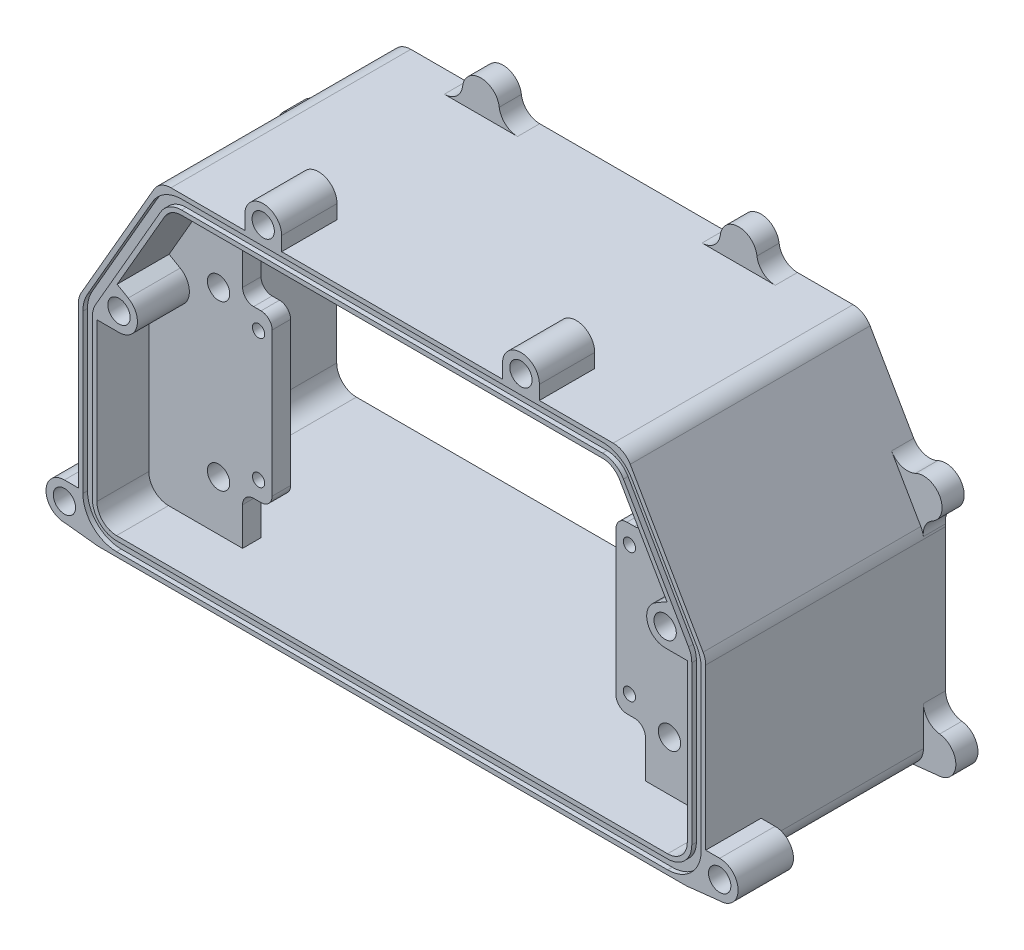
SolidWorks part; units mm, degrees
material "ABS"
ref_plane "X-Y Datum" through (0, 0, 0) normal (0, 0, 1) x (1, 0, 0)
ref_plane "X-Z Datum" through (0, 0, 0) normal (0, 1, 0) x (1, 0, 0)
ref_plane "Y-Z Datum" through (0, 0, 0) normal (1, 0, 0) x (0, 0, -1)
sketch "Sketch1" plane through (0, 0, 0) normal (0, 0, 1) x (1, 0, 0)
  line L0 (-85, -47) -> (-77.6291, 47)
  line L1 (-85, 47) -> (85, 47)
  line L2 (-85, 47) -> (-85, -47)
  line L3 (-85, -47) -> (85, -47)
  line L4 (85, 47) -> (85, -47)
  line L5 (-85, 47) -> (85, -47) construction
  line L6 (-85, -47) -> (85, 47) construction
  line L8 (0, 90.3576) -> (0, -90.3576) construction
  line L9 (85, -47) -> (77.6291, 47)
  point P0 (0, 0)
  point P12 (0, 0)
  dimension "D1" = 170
  dimension "D2" = 94
extrude "Boss-Extrude1" add sketch "Sketch1" along normal mid plane 65 contours L3 L9 L1 L0 | L1 L2 L0 | L9 L4 L1
sketch "Sketch2" plane through (0, 0, -32.5) normal (0, 0, -1) x (-1, 0, 0)
  line L0 (-85, 8.88) -> (-63, 47)
  line L1 (-85, 47) -> (-85, -47) construction
  line L2 (85, 47) -> (-85, 47) construction
  line L3 (0, -14.0019) -> (0, 14.0019) construction
  line L4 (85, 8.88) -> (63, 47)
  point P11 (0, 0)
  line M3 (-85, 47) -> (-85, -47)
  line M5 (85, -47) -> (85, 47)
  line M6 (85, 47) -> (-85, 47)
  dimension "D1" = 55.88
  dimension "D2" = 22
extrude "Cut-Extrude1" cut sketch "Sketch2" against normal through all contours L0 M3 M6 | L4 M5 M6
shell "Shell1" thickness 5
sketch "Sketch4" plane through (0, 0, 27.5) normal (0, 0, -1) x (-1, 0, 0)
  line L6 (-60.1127, 42) -> (-80, 7.5407)
  line L7 (-80, 7.5407) -> (-80, -42)
  line L8 (-80, -42) -> (80, -42)
  line L9 (80, -42) -> (80, 7.5407)
  line L10 (-60.1127, 42) -> (-80, 7.5407)
  line L11 (60.1127, 42) -> (-60.1127, 42)
  line L13 (-80, 7.5407) -> (-80, -42)
  line L14 (-80, -42) -> (80, -42)
  line L15 (80, -42) -> (80, 7.5407)
  line L17 (60.1127, 42) -> (-60.1127, 42)
  line L18 (80, 7.5407) -> (60.1127, 42)
  line L19 (80, 7.5407) -> (60.1127, 42)
  dimension "D1" = 0
extrude "Cut-Extrude2" cut sketch "Sketch4" against normal through all
fillet "Fillet1" radius 5.334 12 edges at (85, 8.88, 0) (63, 47, 0) (-85, 8.88, 0) (-63, 47, 0) (60.1127, 42, 0) (-80, 7.5407, 0) (-80, -42, 0) (80, -42, 0) (-60.1127, 42, 0) (80, 7.5407, 0) (-85, -47, 0) (85, -47, 0)
sketch "Sketch5" plane through (0, 0, 32.5) normal (0, 0, 1) x (1, 0, 0)
  line L44 (-83.7827, 6.1119) -> (-83.7827, -36.666)
  line L45 (-74.666, -45.7827) -> (74.666, -45.7827)
  line L46 (83.7827, -36.666) -> (83.7827, 6.1119)
  line L47 (82.5621, 10.669) -> (64.9286, 41.223)
  line L48 (57.0325, 45.7827) -> (-57.0325, 45.7827)
  line L49 (-64.9286, 41.223) -> (-82.5621, 10.669)
  line L50 (-82.5, 6.1119) -> (-82.5, -36.666)
  line L51 (-74.666, -44.5) -> (74.666, -44.5)
  line L52 (82.5, -36.666) -> (82.5, 6.1119)
  line L53 (81.4511, 10.0278) -> (63.8176, 40.5819)
  line L54 (57.0325, 44.5) -> (-57.0325, 44.5)
  line L55 (-63.8176, 40.5819) -> (-81.4511, 10.0278)
  line L56 (-82.5, 6.1119) -> (-82.5, -36.666) construction
  line L57 (-74.666, -44.5) -> (74.666, -44.5) construction
  line L58 (82.5, -36.666) -> (82.5, 6.1119) construction
  line L59 (81.4511, 10.0278) -> (63.8176, 40.5819) construction
  line L60 (57.0325, 44.5) -> (-57.0325, 44.5) construction
  line L61 (-63.8176, 40.5819) -> (-81.4511, 10.0278) construction
  line L62 (-62.7066, 39.9407) -> (-80.3401, 9.3866)
  line L63 (-81.2173, 6.1119) -> (-81.2173, -36.666)
  line L64 (-74.666, -43.2173) -> (74.666, -43.2173)
  line L65 (81.2173, -36.666) -> (81.2173, 6.1119)
  line L66 (80.3401, 9.3866) -> (62.7066, 39.9407)
  line L67 (57.0325, 43.2173) -> (-57.0325, 43.2173)
  arc A34 (-83.7827, -36.666) -> (-74.666, -45.7827) centre (-74.666, -36.666) ccw
  arc A35 (74.666, -45.7827) -> (83.7827, -36.666) centre (74.666, -36.666) ccw
  arc A36 (83.7827, 6.1119) -> (82.5621, 10.669) centre (74.666, 6.1119) ccw
  arc A37 (64.9286, 41.223) -> (57.0325, 45.7827) centre (57.0325, 36.666) ccw
  arc A38 (-57.0325, 45.7827) -> (-64.9286, 41.223) centre (-57.0325, 36.666) ccw
  arc A39 (-82.5621, 10.669) -> (-83.7827, 6.1119) centre (-74.666, 6.1119) ccw
  arc A40 (-81.4511, 10.0278) -> (-82.5, 6.1119) centre (-74.666, 6.1119) ccw
  arc A41 (-82.5, -36.666) -> (-74.666, -44.5) centre (-74.666, -36.666) ccw
  arc A42 (82.5, 6.1119) -> (81.4511, 10.0278) centre (74.666, 6.1119) ccw
  arc A43 (74.666, -44.5) -> (82.5, -36.666) centre (74.666, -36.666) ccw
  arc A44 (63.8176, 40.5819) -> (57.0325, 44.5) centre (57.0325, 36.666) ccw
  arc A45 (-57.0325, 44.5) -> (-63.8176, 40.5819) centre (-57.0325, 36.666) ccw
  arc A46 (-81.4511, 10.0278) -> (-82.5, 6.1119) centre (-74.666, 6.1119) ccw construction
  arc A47 (-82.5, -36.666) -> (-74.666, -44.5) centre (-74.666, -36.666) ccw construction
  arc A48 (82.5, 6.1119) -> (81.4511, 10.0278) centre (74.666, 6.1119) ccw construction
  arc A49 (74.666, -44.5) -> (82.5, -36.666) centre (74.666, -36.666) ccw construction
  arc A50 (63.8176, 40.5819) -> (57.0325, 44.5) centre (57.0325, 36.666) ccw construction
  arc A51 (-57.0325, 44.5) -> (-63.8176, 40.5819) centre (-57.0325, 36.666) ccw construction
  arc A52 (-80.3401, 9.3866) -> (-81.2173, 6.1119) centre (-74.666, 6.1119) ccw
  arc A53 (-81.2173, -36.666) -> (-74.666, -43.2173) centre (-74.666, -36.666) ccw
  arc A54 (74.666, -43.2173) -> (81.2173, -36.666) centre (74.666, -36.666) ccw
  arc A55 (81.2173, 6.1119) -> (80.3401, 9.3866) centre (74.666, 6.1119) ccw
  arc A56 (62.7066, 39.9407) -> (57.0325, 43.2173) centre (57.0325, 36.666) ccw
  arc A57 (-57.0325, 43.2173) -> (-62.7066, 39.9407) centre (-57.0325, 36.666) ccw
  dimension "D1" = 2.5
  dimension "D2" = 1.2827
  dimension "D3" = 1.2827
extrude "Cut-Extrude3" cut sketch "Sketch5" against normal blind 1.2446
mirror "Mirror1" about plane through (0, 0, 0) normal (0, 0, 1) of "Cut-Extrude3"
sketch "Sketch7" plane through (0, 0, 32.5) normal (0, 0, 1) x (1, 0, 0)
  line L0 (0, 28.7255) -> (0, -28.7255) construction
  line L1 (83.7827, -36.666) -> (83.7827, 6.1119) construction
  line L2 (-79.666, -47) -> (79.666, -47) construction
  line L3 (88.7827, -36) -> (85, -36)
  line L4 (-57.0325, 42) -> (57.0325, 42) construction
  line L5 (85, 7.4512) -> (85, -41.666) construction
  line L6 (-88.7827, -36) -> (-85, -36)
  line L7 (88.7827, -46) -> (79.666, -47)
  line L8 (-88.7827, -46) -> (-79.666, -47)
  line L9 (80, 6.1119) -> (80, -36.666) construction
  line L10 (-59.9198, 47) -> (59.9198, 47) construction
  line L11 (74.504, 17.0638) -> (71.5007, 15.3305)
  line L12 (61.6523, 39.3322) -> (79.2858, 8.7782) construction
  line L13 (-74.504, 17.0638) -> (-71.5007, 15.3305)
  line L14 (-79.2858, 8.7782) -> (-61.6523, 39.3322) construction
  line L15 (74, 6) -> (80, 6)
  line L16 (57.0325, 45.7827) -> (-57.0325, 45.7827) construction
  line L17 (39.9198, 50.7827) -> (39.9198, 47)
  line L18 (-74, 6) -> (-80, 6)
  line L19 (-39.9198, 50.7827) -> (-39.9198, 47)
  line L20 (29.9198, 50.7827) -> (29.9198, 47)
  line L21 (-29.9198, 50.7827) -> (-29.9198, 47)
  line L22 (-80, -36.666) -> (-80, 6.1119) construction
  line L23 (74.666, -42) -> (-74.666, -42) construction
  line L24 (-57.0325, 42) -> (57.0325, 42)
  line L25 (-79.2858, 8.7782) -> (-61.6523, 39.3322)
  line L26 (-80, -36.666) -> (-80, 6.1119)
  line L27 (74.666, -42) -> (-74.666, -42)
  line L28 (80, 6.1119) -> (80, -36.666)
  line L29 (61.6523, 39.3322) -> (79.2858, 8.7782)
  line L30 (85, 7.4512) -> (85, -41.666)
  line L31 (-59.9198, 47) -> (59.9198, 47)
  line L32 (-85, 7.4512) -> (-85, -41.666) construction
  line L33 (-85, 7.4512) -> (-85, -41.666)
  circle A0 centre (88.7827, -41) radius 3.025
  circle A1 centre (34.9198, 50.7827) radius 3.025
  circle A2 centre (74, 11) radius 3.025
  circle A3 centre (88.7827, -41) radius 5
  circle A4 centre (74, 11) radius 5
  circle A5 centre (34.9198, 50.7827) radius 5
  circle A6 centre (-88.7827, -41) radius 3.025
  circle A7 centre (-88.7827, -41) radius 5
  circle A8 centre (-74, 11) radius 3.025
  circle A9 centre (-74, 11) radius 5
  circle A10 centre (-34.9198, 50.7827) radius 5
  circle A11 centre (-34.9198, 50.7827) radius 3.025
  arc A12 (61.6523, 39.3322) -> (57.0325, 42) centre (57.0325, 36.666) ccw construction
  arc A13 (-57.0325, 42) -> (-61.6523, 39.3322) centre (-57.0325, 36.666) ccw construction
  arc A14 (-79.2858, 8.7782) -> (-80, 6.1119) centre (-74.666, 6.1119) ccw construction
  arc A15 (-80, -36.666) -> (-74.666, -42) centre (-74.666, -36.666) ccw construction
  arc A16 (74.666, -42) -> (80, -36.666) centre (74.666, -36.666) ccw construction
  arc A17 (80, 6.1119) -> (79.2858, 8.7782) centre (74.666, 6.1119) ccw construction
  arc A18 (61.6523, 39.3322) -> (57.0325, 42) centre (57.0325, 36.666) ccw
  arc A19 (-57.0325, 42) -> (-61.6523, 39.3322) centre (-57.0325, 36.666) ccw
  arc A20 (-79.2858, 8.7782) -> (-80, 6.1119) centre (-74.666, 6.1119) ccw
  arc A21 (-80, -36.666) -> (-74.666, -42) centre (-74.666, -36.666) ccw
  arc A22 (74.666, -42) -> (80, -36.666) centre (74.666, -36.666) ccw
  arc A23 (80, 6.1119) -> (79.2858, 8.7782) centre (74.666, 6.1119) ccw
  arc A24 (79.666, -47) -> (85, -41.666) centre (79.666, -41.666) ccw construction
  arc A25 (79.666, -47) -> (85, -41.666) centre (79.666, -41.666) ccw
  arc A26 (-85, -41.666) -> (-79.666, -47) centre (-79.666, -41.666) ccw construction
  arc A27 (-85, -41.666) -> (-79.666, -47) centre (-79.666, -41.666) ccw
  point P17 (0, 0)
  point P53 (74, 11)
  point P57 (59.9198, 47)
  point P58 (-59.9198, 47)
  arc M14 (79.666, -47) -> (85, -41.666) centre (79.666, -41.666) ccw
  line M15 (85, -41.666) -> (85, 7.4512)
  line M19 (59.9198, 47) -> (-59.9198, 47)
  dimension "D1" = 6.05
  dimension "D2" = 10
  dimension "D3" = 5
  dimension "D4" = 6
  dimension "D5" = 6
  dimension "D6" = 36
  dimension "D7" = 5
  dimension "D8" = 25
extrude "Boss-Extrude2" add sketch "Sketch7" against normal blind 15 contours A3 L7 M14 | A3 A0 M15 M14 | A3 L3 L30 | A3 M15 M14 | L28 A23 L29 A4 L15 | L29 A4 A2 | A4 L29 L11 | A2 | A0 | A1 | A5 L31 A1 | A5 L17 M19 | A5 L20 M19
sketch "Sketch8" plane through (0, 0, 32.5) normal (0, 0, 1) x (1, 0, 0)
  line L0 (88.7827, -46) -> (79.666, -47) construction
  line L1 (85, 7.4512) -> (85, -41.666) construction
  line L2 (-88.7827, -36) -> (-85, -36) construction
  line L3 (88.7827, -36) -> (85, -36) construction
  line L4 (-88.7827, -46) -> (-79.666, -47) construction
  line L5 (-85, 7.4512) -> (-85, -41.666) construction
  line L6 (-74.666, -42) -> (74.666, -42)
  line L7 (-80, 6.1119) -> (-80, -36.666)
  line L8 (-61.6523, 39.3322) -> (-79.2858, 8.7782)
  line L9 (57.0325, 42) -> (-57.0325, 42)
  line L10 (79.2858, 8.7782) -> (61.6523, 39.3322)
  line L11 (80, -36.666) -> (80, 6.1119)
  line L12 (-74.666, -42) -> (74.666, -42)
  line L13 (-80, 6.1119) -> (-80, -36.666)
  line L14 (-61.6523, 39.3322) -> (-79.2858, 8.7782)
  line L15 (57.0325, 42) -> (-57.0325, 42)
  line L16 (79.2858, 8.7782) -> (61.6523, 39.3322)
  line L17 (80, -36.666) -> (80, 6.1119)
  line L18 (-59.9198, 47) -> (59.9198, 47) construction
  line L19 (-74.504, 17.0638) -> (-71.5007, 15.3305) construction
  line L20 (74.504, 17.0638) -> (71.5007, 15.3305) construction
  line L21 (29.9198, 50.7827) -> (29.9198, 47) construction
  line L22 (-39.9198, 50.7827) -> (-39.9198, 47) construction
  line L23 (-74, 6) -> (-80, 6) construction
  line L24 (39.9198, 50.7827) -> (39.9198, 47) construction
  line L25 (74, 6) -> (80, 6) construction
  line L26 (-29.9198, 50.7827) -> (-29.9198, 47) construction
  line L27 (88.7827, -46) -> (79.666, -47)
  line L28 (85, 7.4512) -> (85, -41.666)
  line L29 (-88.7827, -36) -> (-85, -36)
  line L30 (88.7827, -36) -> (85, -36)
  line L31 (-88.7827, -46) -> (-79.666, -47)
  line L32 (-85, 7.4512) -> (-85, -41.666)
  line L33 (-59.9198, 47) -> (59.9198, 47)
  line L34 (-74.504, 17.0638) -> (-71.5007, 15.3305)
  line L35 (74.504, 17.0638) -> (71.5007, 15.3305)
  line L36 (29.9198, 50.7827) -> (29.9198, 47)
  line L37 (-39.9198, 50.7827) -> (-39.9198, 47)
  line L38 (-74, 6) -> (-80, 6)
  line L39 (39.9198, 50.7827) -> (39.9198, 47)
  line L40 (74, 6) -> (80, 6)
  line L41 (-29.9198, 50.7827) -> (-29.9198, 47)
  arc A0 (79.666, -47) -> (85, -41.666) centre (79.666, -41.666) ccw construction
  circle A1 centre (-74, 11) radius 3.025
  circle A2 centre (-74, 11) radius 3.025
  circle A3 centre (-88.7827, -41) radius 5
  circle A4 centre (-88.7827, -41) radius 5
  circle A5 centre (-88.7827, -41) radius 3.025
  circle A6 centre (-88.7827, -41) radius 3.025
  circle A7 centre (34.9198, 50.7827) radius 5
  circle A8 centre (34.9198, 50.7827) radius 5
  circle A9 centre (74, 11) radius 5
  circle A10 centre (74, 11) radius 5
  circle A11 centre (88.7827, -41) radius 5
  circle A12 centre (88.7827, -41) radius 5
  circle A13 centre (74, 11) radius 3.025
  circle A14 centre (74, 11) radius 3.025
  circle A15 centre (34.9198, 50.7827) radius 3.025
  circle A16 centre (34.9198, 50.7827) radius 3.025
  circle A17 centre (88.7827, -41) radius 3.025
  circle A18 centre (88.7827, -41) radius 3.025
  circle A19 centre (-34.9198, 50.7827) radius 3.025
  circle A20 centre (-34.9198, 50.7827) radius 3.025
  circle A21 centre (-34.9198, 50.7827) radius 5
  circle A22 centre (-34.9198, 50.7827) radius 5
  circle A23 centre (-74, 11) radius 5
  circle A24 centre (-74, 11) radius 5
  arc A25 (-85, -41.666) -> (-79.666, -47) centre (-79.666, -41.666) ccw construction
  arc A26 (79.666, -47) -> (85, -41.666) centre (79.666, -41.666) ccw
  arc A27 (-85, -41.666) -> (-79.666, -47) centre (-79.666, -41.666) ccw
  arc A30 (-80, -36.666) -> (-74.666, -42) centre (-74.666, -36.666) ccw
  arc A31 (-79.2858, 8.7782) -> (-80, 6.1119) centre (-74.666, 6.1119) ccw
  arc A32 (-57.0325, 42) -> (-61.6523, 39.3322) centre (-57.0325, 36.666) ccw
  arc A33 (61.6523, 39.3322) -> (57.0325, 42) centre (57.0325, 36.666) ccw
  arc A34 (80, 6.1119) -> (79.2858, 8.7782) centre (74.666, 6.1119) ccw
  arc A35 (74.666, -42) -> (80, -36.666) centre (74.666, -36.666) ccw
  arc A36 (-80, -36.666) -> (-74.666, -42) centre (-74.666, -36.666) ccw
  arc A37 (-79.2858, 8.7782) -> (-80, 6.1119) centre (-74.666, 6.1119) ccw
  arc A38 (-57.0325, 42) -> (-61.6523, 39.3322) centre (-57.0325, 36.666) ccw
  arc A39 (61.6523, 39.3322) -> (57.0325, 42) centre (57.0325, 36.666) ccw
  arc A40 (80, 6.1119) -> (79.2858, 8.7782) centre (74.666, 6.1119) ccw
  arc A41 (74.666, -42) -> (80, -36.666) centre (74.666, -36.666) ccw
  dimension "D1" = 0
  dimension "D2" = 0
  dimension "D3" = 0
  dimension "D4" = 0
  dimension "D5" = 0
  dimension "D6" = 0
  dimension "D7" = 0
  dimension "D8" = 0
  dimension "D9" = 0
  dimension "D10" = 0
  dimension "D11" = 0
  dimension "D12" = 0
  dimension "D13" = 0
extrude "Cut-Extrude4" cut sketch "Sketch8" against normal blind 8 contours A16 | A14 | A18
mirror "Mirror2" about plane through (0, 0, 0) normal (1, 0, 0) of "Cut-Extrude4", "Boss-Extrude2"
ref_plane "Plane1" through (0, 0, 18.42) normal (0, 0, -1) x (-1, 0, 0)
sketch "Sketch9" plane through (0, 0, 18.42) normal (0, 0, -1) x (-1, 0, 0)
  line L0 (61.09, 15.9688) -> (61.09, -28.4812) construction
  line L1 (74.666, -42) -> (-74.666, -42) construction
  line L2 (54.59, -42) -> (67.59, -42)
  line L3 (54.59, -42) -> (54.59, 29.0439)
  line L4 (54.59, 29.0439) -> (67.59, 29.0439)
  line L5 (67.59, -42) -> (67.59, 29.0439)
  line L6 (79.2858, 8.7782) -> (61.6523, 39.3322) construction
  line L7 (61.09, 29.0439) -> (61.09, -42) construction
  line L8 (54.59, 29.0439) -> (54.59, 42)
  line L9 (57.0325, 42) -> (-57.0325, 42) construction
  line L10 (79.2858, 8.7782) -> (61.6523, 39.3322)
  line L11 (57.0325, 42) -> (-57.0325, 42)
  line L13 (80, 6.1119) -> (80, -36.666) construction
  line L14 (74.666, -42) -> (-74.666, -42)
  line L15 (80, 6.1119) -> (80, -36.666)
  arc A0 (61.6523, 39.3322) -> (57.0325, 42) centre (57.0325, 36.666) ccw construction
  arc A1 (61.6523, 39.3322) -> (57.0325, 42) centre (57.0325, 36.666) ccw
  circle A2 centre (61.09, 15.9688) radius 3.025
  circle A3 centre (61.09, -28.4812) radius 3.025
  arc A4 (74.666, -42) -> (80, -36.666) centre (74.666, -36.666) ccw construction
  arc A5 (80, 6.1119) -> (79.2858, 8.7782) centre (74.666, 6.1119) ccw construction
  arc A6 (74.666, -42) -> (80, -36.666) centre (74.666, -36.666) ccw
  arc A7 (80, 6.1119) -> (79.2858, 8.7782) centre (74.666, 6.1119) ccw
  point P0 (-61.09, 15.9688)
  point P1 (-61.09, -28.4812)
  point P3 (61.09, -28.4812)
  point P5 (61.09, 15.9688)
  dimension "D2" = 6.05
  dimension "D1" = 13
extrude "Boss-Extrude3" add sketch "Sketch9" along normal blind 5 contours L10 A1 L11 L8 L4 | L2 L5 L4 L3 A3 A2 | L15 A7 L10 L5 L14 A6
mirror "Mirror3" about plane through (0, 0, 0) normal (1, 0, 0) of "Boss-Extrude3"
sketch "Sketch10" plane through (0, 0, 13.42) normal (0, 0, -1) x (-1, 0, 0)
  line L0 (50.25, 11.2438) -> (50.25, -23.7562) construction
  line L2 (54.59, -28.7562) -> (46.59, -28.7562)
  line L3 (54.59, -28.7562) -> (54.59, 16.2438)
  line L4 (54.59, 16.2438) -> (46.59, 16.2438)
  line L5 (46.59, -28.7562) -> (46.59, 16.2438)
  line L6 (46.59, -6.2562) -> (54.59, -6.2562)
  line L7 (43.6754, -6.2562) -> (56.8246, -6.2562) construction
  line L13 (79.2858, 8.7782) -> (61.6523, 39.3322)
  line L14 (57.0325, 42) -> (54.59, 42)
  line L15 (54.59, 42) -> (54.59, -42)
  line L16 (54.59, -42) -> (74.666, -42)
  line L17 (80, -36.666) -> (80, 6.1119)
  line L18 (79.2858, 8.7782) -> (61.6523, 39.3322)
  line L19 (57.0325, 42) -> (54.59, 42)
  line L20 (54.59, 42) -> (54.59, -42)
  line L21 (54.59, -42) -> (74.666, -42)
  line L22 (80, -36.666) -> (80, 6.1119)
  circle A0 centre (50.25, -23.7562) radius 1.665
  circle A1 centre (50.25, 11.2438) radius 1.665
  arc A5 (61.6523, 39.3322) -> (57.0325, 42) centre (57.0325, 36.666) ccw
  arc A6 (74.666, -42) -> (80, -36.666) centre (74.666, -36.666) ccw
  arc A7 (80, 6.1119) -> (79.2858, 8.7782) centre (74.666, 6.1119) ccw
  arc A8 (61.6523, 39.3322) -> (57.0325, 42) centre (57.0325, 36.666) ccw
  arc A9 (74.666, -42) -> (80, -36.666) centre (74.666, -36.666) ccw
  arc A10 (80, 6.1119) -> (79.2858, 8.7782) centre (74.666, 6.1119) ccw
  point P0 (50.25, 11.2438)
  point P1 (50.25, -23.7562)
  point P6 (50.25, -6.2562)
  point P18 (50.25, -6.2562)
  line M11 (54.59, 42) -> (54.59, -42)
  dimension "D3" = 3.33
  dimension "D1" = 8
  dimension "D2" = 45
  dimension "D4" = 0
extrude "Boss-Extrude4" add sketch "Sketch10" against normal blind 5 separate body contours L6 L5 L2 L3 | L5 L6 L4 M11
mirror "Mirror9" about plane through (0, 0, 0) normal (1, 0, 0) of bodies 115
combine bodies "Combine2" operation type add bodies to combine 114 115 117
fillet "Fillet2" radius 3 8 edges at (-54.59, 16.2438, 15.92) (-54.59, -28.7562, 15.92) (-46.59, -28.7562, 15.92) (-46.59, 16.2438, 15.92) (54.59, -28.7562, 15.92) (46.59, -28.7562, 15.92) (46.59, 16.2438, 15.92) (54.59, 16.2438, 15.92)
sketch "Sketch11" plane through (0, 0, -32.5) normal (0, 0, -1) x (-1, 0, 0)
  line L0 (-88.7827, -46) -> (-79.666, -47) construction
  line L1 (-85, 7.4512) -> (-85, -41.666) construction
  line L2 (88.7827, -36) -> (85, -36) construction
  line L3 (-88.7827, -36) -> (-85, -36) construction
  line L4 (88.7827, -46) -> (79.666, -47) construction
  line L5 (85, 7.4512) -> (85, -41.666) construction
  line L6 (-74.666, -42) -> (74.666, -42)
  line L7 (80, -36.666) -> (80, 6.1119)
  line L8 (79.2858, 8.7782) -> (61.6523, 39.3322)
  line L9 (57.0325, 42) -> (-57.0325, 42)
  line L10 (-61.6523, 39.3322) -> (-79.2858, 8.7782)
  line L11 (-80, 6.1119) -> (-80, -36.666)
  line L12 (-74.666, -42) -> (74.666, -42)
  line L13 (80, -36.666) -> (80, 6.1119)
  line L14 (79.2858, 8.7782) -> (61.6523, 39.3322)
  line L15 (57.0325, 42) -> (-57.0325, 42)
  line L16 (-61.6523, 39.3322) -> (-79.2858, 8.7782)
  line L17 (-80, 6.1119) -> (-80, -36.666)
  line L18 (59.9198, 47) -> (-59.9198, 47) construction
  line L19 (74.504, 17.0638) -> (71.5007, 15.3305) construction
  line L20 (-74.504, 17.0638) -> (-71.5007, 15.3305) construction
  line L21 (-29.9198, 50.7827) -> (-29.9198, 47) construction
  line L22 (39.9198, 50.7827) -> (39.9198, 47) construction
  line L23 (74, 6) -> (80, 6) construction
  line L24 (-39.9198, 50.7827) -> (-39.9198, 47) construction
  line L25 (-74, 6) -> (-80, 6) construction
  line L26 (29.9198, 50.7827) -> (29.9198, 47) construction
  line L27 (-88.7827, -46) -> (-79.666, -47)
  line L28 (-85, 7.4512) -> (-85, -41.666)
  line L29 (88.7827, -36) -> (85, -36)
  line L30 (-88.7827, -36) -> (-85, -36)
  line L31 (88.7827, -46) -> (79.666, -47)
  line L32 (85, 7.4512) -> (85, -41.666)
  line L33 (59.9198, 47) -> (-59.9198, 47)
  line L34 (74.504, 17.0638) -> (71.5007, 15.3305)
  line L35 (-74.504, 17.0638) -> (-71.5007, 15.3305)
  line L36 (-29.9198, 50.7827) -> (-29.9198, 47)
  line L37 (39.9198, 50.7827) -> (39.9198, 47)
  line L38 (74, 6) -> (80, 6)
  line L39 (-39.9198, 50.7827) -> (-39.9198, 47)
  line L40 (-74, 6) -> (-80, 6)
  line L41 (29.9198, 50.7827) -> (29.9198, 47)
  line L42 (-74, 11) -> (-85.0431, 17.3732)
  line L43 (-82.5621, 10.669) -> (-64.9286, 41.223) construction
  line L44 (-82.5438, 21.7038) -> (-78.8345, 19.5631)
  line L45 (-84.2858, 10.1175) -> (-64.5396, 44.3322) construction
  line L46 (-87.5424, 13.0427) -> (-83.8331, 10.902)
  line L47 (-84.2858, 10.1175) -> (-64.5396, 44.3322)
  line L49 (-31.0762, 0) -> (31.0762, 0) construction
  line L50 (59.9198, -47) -> (-59.9198, -47)
  line L51 (-39.9198, -50.7827) -> (-39.9198, -47)
  line L52 (-29.9198, -50.7827) -> (-29.9198, -47)
  arc A0 (-85, -41.666) -> (-79.666, -47) centre (-79.666, -41.666) ccw construction
  circle A1 centre (74, 11) radius 3.025
  circle A2 centre (74, 11) radius 3.025
  circle A3 centre (88.7827, -41) radius 5
  circle A4 centre (88.7827, -41) radius 5
  circle A5 centre (88.7827, -41) radius 3.025
  circle A6 centre (88.7827, -41) radius 3.025
  circle A7 centre (-34.9198, 50.7827) radius 5
  circle A8 centre (-34.9198, 50.7827) radius 5
  circle A9 centre (-74, 11) radius 5
  circle A10 centre (-74, 11) radius 5
  circle A11 centre (-88.7827, -41) radius 5
  circle A12 centre (-88.7827, -41) radius 5
  circle A13 centre (-74, 11) radius 3.025
  circle A14 centre (-74, 11) radius 3.025
  circle A15 centre (-34.9198, 50.7827) radius 3.025
  circle A16 centre (-34.9198, 50.7827) radius 3.025
  circle A17 centre (-88.7827, -41) radius 3.025
  circle A18 centre (-88.7827, -41) radius 3.025
  circle A19 centre (34.9198, 50.7827) radius 3.025
  circle A20 centre (34.9198, 50.7827) radius 3.025
  circle A21 centre (34.9198, 50.7827) radius 5
  circle A22 centre (34.9198, 50.7827) radius 5
  circle A23 centre (74, 11) radius 5
  circle A24 centre (74, 11) radius 5
  arc A25 (79.666, -47) -> (85, -41.666) centre (79.666, -41.666) ccw construction
  arc A26 (-85, -41.666) -> (-79.666, -47) centre (-79.666, -41.666) ccw
  arc A27 (79.666, -47) -> (85, -41.666) centre (79.666, -41.666) ccw
  circle A28 centre (-85.0431, 17.3732) radius 3.025
  circle A29 centre (-85.0431, 17.3732) radius 5
  arc A30 (74.666, -42) -> (80, -36.666) centre (74.666, -36.666) ccw
  arc A31 (80, 6.1119) -> (79.2858, 8.7782) centre (74.666, 6.1119) ccw
  arc A32 (61.6523, 39.3322) -> (57.0325, 42) centre (57.0325, 36.666) ccw
  arc A33 (-57.0325, 42) -> (-61.6523, 39.3322) centre (-57.0325, 36.666) ccw
  arc A34 (-79.2858, 8.7782) -> (-80, 6.1119) centre (-74.666, 6.1119) ccw
  arc A35 (-80, -36.666) -> (-74.666, -42) centre (-74.666, -36.666) ccw
  arc A36 (74.666, -42) -> (80, -36.666) centre (74.666, -36.666) ccw
  arc A37 (80, 6.1119) -> (79.2858, 8.7782) centre (74.666, 6.1119) ccw
  arc A38 (61.6523, 39.3322) -> (57.0325, 42) centre (57.0325, 36.666) ccw
  arc A39 (-57.0325, 42) -> (-61.6523, 39.3322) centre (-57.0325, 36.666) ccw
  arc A40 (-79.2858, 8.7782) -> (-80, 6.1119) centre (-74.666, 6.1119) ccw
  arc A41 (-80, -36.666) -> (-74.666, -42) centre (-74.666, -36.666) ccw
  circle A44 centre (-34.9198, -50.7827) radius 3.025
  circle A45 centre (-34.9198, -50.7827) radius 5
  point P91 (-82.4231, 15.8612)
  point P98 (85.7577, -41)
  point P105 (0, 0)
  point P111 (-34.9198, -45.7827)
  point P112 (-34.9198, -47.7577)
  dimension "D14" = 5.5
  dimension "D1" = 0
  dimension "D2" = 0
  dimension "D3" = 0
  dimension "D4" = 0
  dimension "D5" = 0
  dimension "D6" = 0
  dimension "D7" = 0
  dimension "D8" = 0
  dimension "D9" = 0
  dimension "D10" = 0
  dimension "D11" = 0
  dimension "D12" = 0
  dimension "D13" = 0
extrude "Boss-Extrude5" add sketch "Sketch11" against normal blind 6
sketch "Sketch12" plane through (0, 0, -32.5) normal (0, 0, -1) x (-1, 0, 0)
  line L0 (-74, 11) -> (-85.0431, 17.3732) construction
  line L1 (-85, 7.4512) -> (-85, -41.666) construction
  line L2 (-88.7827, -46) -> (-79.666, -47) construction
  line L3 (-88.7827, -36) -> (-85, -36) construction
  line L4 (88.7827, -36) -> (85, -36) construction
  line L5 (-29.9198, 50.7827) -> (-29.9198, 47) construction
  line L6 (57.0325, 42) -> (-57.0325, 42)
  line L7 (-61.6523, 39.3322) -> (-79.2858, 8.7782)
  line L8 (-80, 6.1119) -> (-80, -36.666)
  line L9 (-74.666, -42) -> (74.666, -42)
  line L10 (80, -36.666) -> (80, 6.1119)
  line L11 (79.2858, 8.7782) -> (61.6523, 39.3322)
  line L12 (57.0325, 42) -> (-57.0325, 42)
  line L13 (-61.6523, 39.3322) -> (-79.2858, 8.7782)
  line L14 (-80, 6.1119) -> (-80, -36.666)
  line L15 (-74.666, -42) -> (74.666, -42)
  line L16 (80, -36.666) -> (80, 6.1119)
  line L17 (79.2858, 8.7782) -> (61.6523, 39.3322)
  line L18 (-74.504, 17.0638) -> (-71.5007, 15.3305) construction
  line L19 (74.504, 17.0638) -> (71.5007, 15.3305) construction
  line L20 (59.9198, 47) -> (-59.9198, 47) construction
  line L21 (88.7827, -46) -> (79.666, -47) construction
  line L22 (85, 7.4512) -> (85, -41.666) construction
  line L23 (-84.2858, 10.1175) -> (-64.5396, 44.3322) construction
  line L24 (-82.5438, 21.7038) -> (-78.8345, 19.5631) construction
  line L25 (29.9198, 50.7827) -> (29.9198, 47) construction
  line L26 (-74, 6) -> (-80, 6) construction
  line L27 (-39.9198, 50.7827) -> (-39.9198, 47) construction
  line L28 (74, 6) -> (80, 6) construction
  line L29 (39.9198, 50.7827) -> (39.9198, 47) construction
  line L30 (-87.5424, 13.0427) -> (-83.8331, 10.902) construction
  line L31 (-74, 11) -> (-85.0431, 17.3732)
  line L32 (-85, 7.4512) -> (-85, -41.666)
  line L33 (-88.7827, -46) -> (-79.666, -47)
  line L34 (-88.7827, -36) -> (-85, -36)
  line L35 (88.7827, -36) -> (85, -36)
  line L36 (-29.9198, 50.7827) -> (-29.9198, 47)
  line L37 (-74.504, 17.0638) -> (-71.5007, 15.3305)
  line L38 (74.504, 17.0638) -> (71.5007, 15.3305)
  line L39 (59.9198, 47) -> (-59.9198, 47)
  line L40 (88.7827, -46) -> (79.666, -47)
  line L41 (85, 7.4512) -> (85, -41.666)
  line L42 (-84.2858, 10.1175) -> (-64.5396, 44.3322)
  line L43 (-82.5438, 21.7038) -> (-78.8345, 19.5631)
  line L44 (29.9198, 50.7827) -> (29.9198, 47)
  line L45 (-74, 6) -> (-80, 6)
  line L46 (-39.9198, 50.7827) -> (-39.9198, 47)
  line L47 (74, 6) -> (80, 6)
  line L48 (39.9198, 50.7827) -> (39.9198, 47)
  line L49 (-87.5424, 13.0427) -> (-83.8331, 10.902)
  line L50 (-29.9198, -50.7827) -> (-29.9198, -47) construction
  line L51 (-39.9198, -50.7827) -> (-39.9198, -47) construction
  line L52 (59.9198, -47) -> (-59.9198, -47) construction
  line L53 (-74, 11) -> (-85.0431, 17.3732)
  line L54 (-85, 7.4512) -> (-85, -41.666)
  line L55 (-88.7827, -46) -> (-79.666, -47)
  line L68 (-88.7827, -36) -> (-85, -36)
  line L69 (88.7827, -36) -> (85, -36)
  line L70 (-29.9198, 50.7827) -> (-29.9198, 47)
  line L71 (-74.504, 17.0638) -> (-71.5007, 15.3305)
  line L72 (74.504, 17.0638) -> (71.5007, 15.3305)
  line L73 (59.9198, 47) -> (-59.9198, 47)
  line L74 (88.7827, -46) -> (79.666, -47)
  line L75 (85, 7.4512) -> (85, -41.666)
  line L76 (-84.2858, 10.1175) -> (-64.5396, 44.3322)
  line L77 (-82.5438, 21.7038) -> (-78.8345, 19.5631)
  line L78 (29.9198, 50.7827) -> (29.9198, 47)
  line L79 (-74, 6) -> (-80, 6)
  line L80 (-39.9198, 50.7827) -> (-39.9198, 47)
  line L81 (74, 6) -> (80, 6)
  line L82 (39.9198, 50.7827) -> (39.9198, 47)
  line L83 (-29.9198, -50.7827) -> (-29.9198, -47)
  line L84 (-39.9198, -50.7827) -> (-39.9198, -47)
  line L85 (59.9198, -47) -> (-59.9198, -47)
  line L86 (-87.5424, 13.0427) -> (-83.8331, 10.902)
  arc A0 (-85, -41.666) -> (-79.666, -47) centre (-79.666, -41.666) ccw construction
  circle A1 centre (-34.9198, 50.7827) radius 5
  circle A2 centre (-34.9198, 50.7827) radius 5
  circle A3 centre (88.7827, -41) radius 3.025
  circle A4 centre (88.7827, -41) radius 3.025
  circle A5 centre (88.7827, -41) radius 5
  circle A6 centre (88.7827, -41) radius 5
  circle A7 centre (74, 11) radius 3.025
  circle A8 centre (74, 11) radius 3.025
  circle A9 centre (34.9198, 50.7827) radius 3.025
  circle A10 centre (34.9198, 50.7827) radius 3.025
  circle A11 centre (-88.7827, -41) radius 3.025
  circle A12 centre (-88.7827, -41) radius 3.025
  circle A13 centre (-34.9198, 50.7827) radius 3.025
  circle A14 centre (-34.9198, 50.7827) radius 3.025
  circle A15 centre (-74, 11) radius 3.025
  circle A16 centre (-74, 11) radius 3.025
  circle A17 centre (-88.7827, -41) radius 5
  circle A18 centre (-88.7827, -41) radius 5
  circle A19 centre (-74, 11) radius 5
  circle A20 centre (-74, 11) radius 5
  circle A21 centre (74, 11) radius 5
  circle A22 centre (74, 11) radius 5
  circle A23 centre (34.9198, 50.7827) radius 5
  circle A24 centre (34.9198, 50.7827) radius 5
  circle A25 centre (-85.0431, 17.3732) radius 5
  circle A26 centre (-85.0431, 17.3732) radius 5
  circle A27 centre (-85.0431, 17.3732) radius 3.025
  circle A28 centre (-85.0431, 17.3732) radius 3.025
  arc A29 (79.666, -47) -> (85, -41.666) centre (79.666, -41.666) ccw construction
  arc A30 (-85, -41.666) -> (-79.666, -47) centre (-79.666, -41.666) ccw
  arc A31 (79.666, -47) -> (85, -41.666) centre (79.666, -41.666) ccw
  arc A32 (-57.0325, 42) -> (-61.6523, 39.3322) centre (-57.0325, 36.666) ccw
  arc A33 (-79.2858, 8.7782) -> (-80, 6.1119) centre (-74.666, 6.1119) ccw
  arc A34 (-80, -36.666) -> (-74.666, -42) centre (-74.666, -36.666) ccw
  arc A35 (74.666, -42) -> (80, -36.666) centre (74.666, -36.666) ccw
  arc A36 (80, 6.1119) -> (79.2858, 8.7782) centre (74.666, 6.1119) ccw
  arc A37 (61.6523, 39.3322) -> (57.0325, 42) centre (57.0325, 36.666) ccw
  arc A38 (-57.0325, 42) -> (-61.6523, 39.3322) centre (-57.0325, 36.666) ccw
  arc A39 (-79.2858, 8.7782) -> (-80, 6.1119) centre (-74.666, 6.1119) ccw
  arc A40 (-80, -36.666) -> (-74.666, -42) centre (-74.666, -36.666) ccw
  arc A41 (74.666, -42) -> (80, -36.666) centre (74.666, -36.666) ccw
  arc A42 (80, 6.1119) -> (79.2858, 8.7782) centre (74.666, 6.1119) ccw
  arc A43 (61.6523, 39.3322) -> (57.0325, 42) centre (57.0325, 36.666) ccw
  arc A44 (-85, -41.666) -> (-79.666, -47) centre (-79.666, -41.666) ccw
  circle A73 centre (-34.9198, -50.7827) radius 5
  circle A74 centre (-34.9198, -50.7827) radius 5
  circle A75 centre (-34.9198, -50.7827) radius 3.025
  circle A88 centre (-34.9198, -50.7827) radius 3.025
  arc A89 (79.666, -47) -> (85, -41.666) centre (79.666, -41.666) ccw
  dimension "D1" = 0
  dimension "D2" = 0
  dimension "D3" = 0
  dimension "D4" = 0
  dimension "D5" = 0
  dimension "D6" = 0
  dimension "D7" = 0
  dimension "D8" = 0
  dimension "D9" = 0
  dimension "D10" = 0
  dimension "D11" = 0
  dimension "D12" = 0
  dimension "D13" = 0
  dimension "D14" = 0
  dimension "D15" = 0
  dimension "D31" = 0
  dimension "D32" = 0
extrude "Cut-Extrude5" cut sketch "Sketch12" against normal blind 5 and the other way through all
fillet "Fillet3" radius 5 7 edges at (29.9198, -47, -29.5) (39.9198, -47, -29.5) (85, -36, -29.5) (29.9198, 47, -29.5) (39.9198, 47, -29.5) (78.8345, 19.5631, -29.5) (83.8331, 10.902, -29.5)
mirror "Mirror14" about plane through (0, 0, 0) normal (1, 0, 0) of "Cut-Extrude5", "Boss-Extrude5"
fillet "Fillet4" radius 5 7 edges at (-29.9198, 47, -29.5) (-39.9198, 47, -29.5) (-78.8345, 19.5631, -29.5) (-83.8331, 10.902, -29.5) (-85, -36, -29.5) (-39.9198, -47, -29.5) (-29.9198, -47, -29.5)
